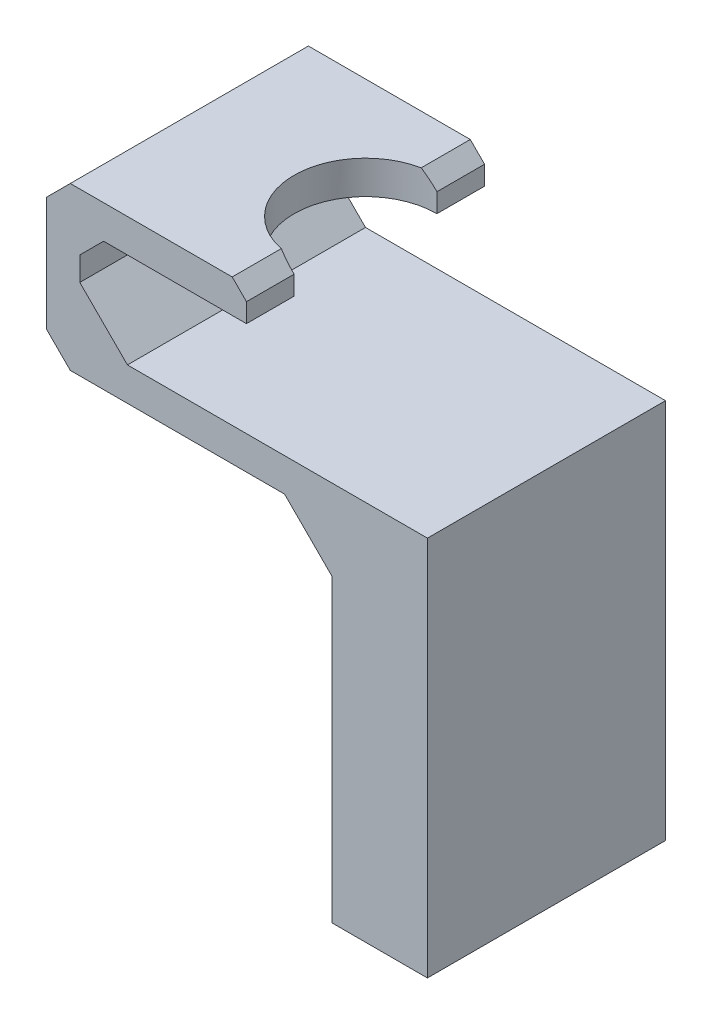
SolidWorks part; units mm, degrees
ref_plane "Plan de face" through (0, 0, 0) normal (0, 0, 1) x (1, 0, 0)
ref_plane "Plan de dessus" through (0, 0, 0) normal (0, 1, 0) x (1, 0, 0)
ref_plane "Plan de droite" through (0, 0, 0) normal (1, 0, 0) x (0, 0, -1)
sketch "Esquisse1" plane through (0, 0, 0) normal (0, 0, 1) x (1, 0, 0)
  line L0 (-10.6886, 25.2949) -> (-52.6886, 25.2949)
  line L1 (-52.6886, 25.2949) -> (-52.6886, -8.7051)
  line L2 (-52.6886, -8.7051) -> (7.3114, -8.7051)
  line L3 (7.3114, -8.7051) -> (7.3114, -81.7051)
  line L4 (7.3114, -81.7051) -> (27.3114, -81.7051)
  line L5 (27.3114, -81.7051) -> (27.3114, -1.7051)
  line L6 (27.3114, -1.7051) -> (-45.6886, -1.7051)
  line L7 (-45.6886, -1.7051) -> (-45.6886, 18.2949)
  line L8 (-45.6886, 18.2949) -> (-10.6886, 18.2949)
  line L9 (-10.6886, 18.2949) -> (-10.6886, 25.2949)
  dimension "D5" = 35
  dimension "D1" = 7
  dimension "D2" = 20
  dimension "D3" = 80
  dimension "D4" = 73
  dimension "D6" = 42
  dimension "D7" = 60
  dimension "D8" = 20
extrude "Boss.-Extru.1" add sketch "Esquisse1" against normal blind 50 contours L5 L6 L7 L8 L9 L0 L1 L2 L3 L4
chamfer "Chanfrein1" distance 10 angle 45 1 edges at (-45.6886, -1.7051, -25)
chamfer "Chanfrein2" distance 10 angle 45 1 edges at (7.3114, -8.7051, -25)
chamfer "Chanfrein3" distance 5 angle 45 1 edges at (-45.6886, 18.2949, -25)
sketch "Esquisse3" plane through (0, 25.2949, 0) normal (0, 1, 0) x (1, 0, 0)
  line L0 (-10.6886, 50) -> (-10.6886, 0) construction
  circle A0 centre (-10.6886, 25) radius 15
  dimension "D1" = 30
  dimension "D2" = 25
extrude "Enlèv. mat.-Extru.1" cut sketch "Esquisse3" against normal blind 7
chamfer "Chanfrein4" distance 5 angle 45 1 edges at (-52.6886, -8.7051, -25)
chamfer "Chanfrein5" distance 5 angle 45 1 edges at (-52.6886, 25.2949, -25)
chamfer "Chanfrein6" distance 3 angle 45 1 edges at (-10.6886, 25.2949, -5)
chamfer "Chanfrein7" distance 3 angle 45 1 edges at (-10.6886, 25.2949, -45)
